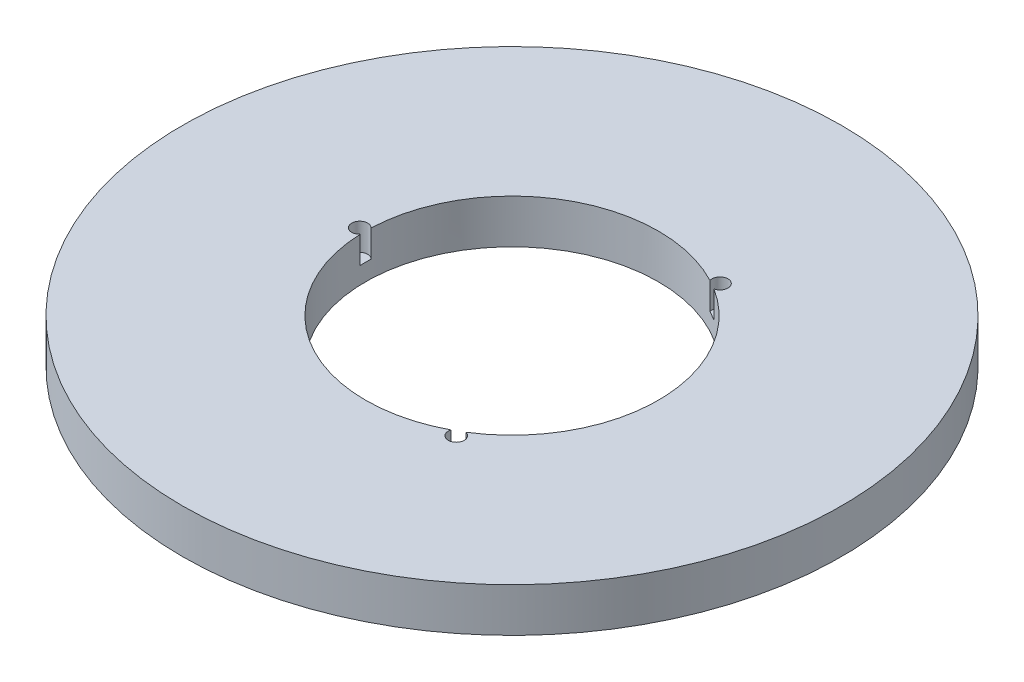
SolidWorks part; units mm, degrees
ref_plane "Front Plane" through (0, 0, 0) normal (0, 0, 1) x (1, 0, 0)
ref_plane "Top Plane" through (0, 0, 0) normal (0, 1, 0) x (1, 0, 0)
ref_plane "Right Plane" through (0, 0, 0) normal (1, 0, 0) x (0, 0, -1)
sketch "Sketch1" plane through (0, 0, 0) normal (0, 1, 0) x (1, 0, 0)
  circle A0 centre (0, 0) radius 90
  dimension "FLANGE_OD" = 180
extrude "Boss-Extrude1" add sketch "Sketch1" along normal blind 12
sketch "Sketch2" plane through (0, 0, 0) normal (0, 1, 0) x (1, 0, 0)
  circle A0 centre (0, 0) radius 40
  dimension "BORE_D" = 80
extrude "Cut-Extrude1" cut sketch "Sketch2" along normal through all
sketch "Sketch3" plane through (0, 12, 0) normal (0, 1, 0) x (1, 0, 0)
  circle A0 centre (0, 0) radius 41.5867 construction
  circle A1 centre (-41.5867, 0) radius 2.1841
  dimension "BOLT_D" = 4.3682
  dimension "BOLT_PCD" = 83.1734
extrude "Cut-Extrude2" cut sketch "Sketch3" against normal blind 7.3786
pattern_circular "CirPattern1" count 3 over 360 about axis through (0, 0, 0) along (0, 1, 0) of "Cut-Extrude2"
